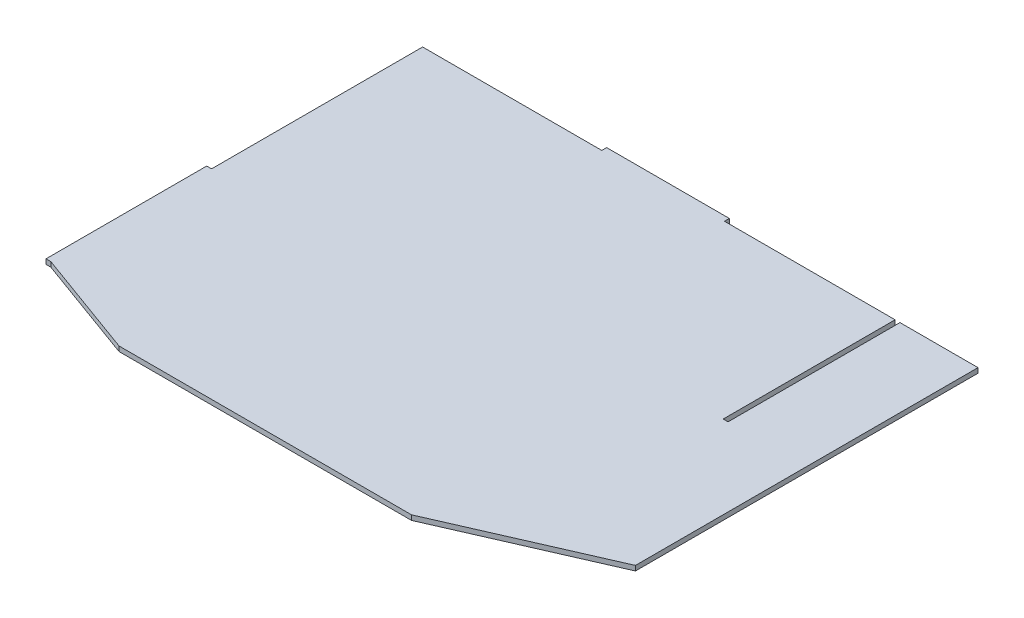
SolidWorks part; units mm, degrees
material "6061-T6 (SS)"
ref_plane "X-Y Datum" through (0, 0, 0) normal (0, 0, 1) x (1, 0, 0)
ref_plane "X-Z Datum" through (0, 0, 0) normal (0, 1, 0) x (1, 0, 0)
ref_plane "Y-Z Datum" through (0, 0, 0) normal (1, 0, 0) x (0, 0, -1)
sketch "Sketch1" plane through (0, 0, 0) normal (0, 0, 1) x (1, 0, 0)
  line L1 (-154.0556, -1.5875) -> (154.0556, -1.5875)
  line L2 (-154.0556, -1.5875) -> (-154.0556, 1.5875)
  line L3 (-154.0556, 1.5875) -> (154.0556, 1.5875)
  line L4 (154.0556, -1.5875) -> (154.0556, 1.5875)
  line L5 (-154.0556, -1.5875) -> (154.0556, 1.5875) construction
  line L6 (-154.0556, 1.5875) -> (154.0556, -1.5875) construction
  point P0 (0, 0)
  dimension "D1" = 3.175
  dimension "D2" = 308.1112
extrude "Boss-Extrude1" add sketch "Sketch1" along normal blind 267.83
sketch "Sketch3" plane through (154.0556, 0, 0) normal (1, 0, 0) x (0, 0, -1)
  line L0 (-267.83, 1.5875) -> (0, 1.5875) construction
  line L1 (-267.83, -1.5875) -> (-112.128, -1.5875)
  line L2 (-267.83, -1.5875) -> (-267.83, 1.5875)
  line L3 (-267.83, 1.5875) -> (-112.128, 1.5875)
  line L4 (-112.128, -1.5875) -> (-112.128, 1.5875)
  dimension "D1" = 155.702
extrude "Boss-Extrude3" add sketch "Sketch3" along normal blind 3.175
sketch "Sketch4" plane through (0, 0, 267.83) normal (0, 0, 1) x (1, 0, 0)
  line L1 (157.2306, -1.5875) -> (208.1043, -1.5875)
  line L2 (157.2306, -1.5875) -> (157.2306, 1.5875)
  line L3 (157.2306, 1.5875) -> (208.1043, 1.5875)
  line L4 (208.1043, -1.5875) -> (208.1043, 1.5875)
  dimension "D1" = 3.175
  dimension "D2" = 50.8737
extrude "Boss-Extrude4" add sketch "Sketch4" against normal blind 267.83
sketch "Sketch6" plane through (0, 1.5875, 0) normal (0, 1, 0) x (1, 0, 0)
  line L0 (106.5043, -267.83) -> (106.5043, -223.38)
  line L1 (208.1043, -267.83) -> (-154.0556, -267.83) construction
  line L2 (208.1043, -223.38) -> (106.5043, -223.38)
  line L3 (208.1043, 0) -> (208.1043, -267.83) construction
  line L4 (106.5043, -267.83) -> (208.1043, -223.38)
  line M9 (-154.0556, -267.83) -> (208.1043, -267.83)
  line M10 (208.1043, -267.83) -> (208.1043, 0)
  dimension "D1" = 44.45
  dimension "D2" = 101.6
extrude "Cut-Extrude1" cut sketch "Sketch6" against normal through all contours L4 M9 M10 region at (174.2376, 1.5875, 253.0133)
sketch "Sketch8" plane through (0, 0, 0) normal (0, 0, -1) x (-1, 0, 0)
  line L1 (37.216, 1.5875) -> (-42.784, 1.5875)
  line L2 (37.216, 1.5875) -> (37.216, -1.5875)
  line L3 (37.216, -1.5875) -> (-42.784, -1.5875)
  line L4 (-42.784, 1.5875) -> (-42.784, -1.5875)
extrude "Boss-Extrude6" add sketch "Sketch8" along normal blind 3.175
sketch "Sketch11" plane through (0, -1.5875, 0) normal (0, -1, 0) x (1, 0, 0)
  line L0 (-84.2056, 267.83) -> (-84.2056, 242.43)
  line L1 (-154.0556, 267.83) -> (106.5043, 267.83) construction
  line L2 (-154.0556, 242.43) -> (-84.2056, 242.43)
  line L3 (-154.0556, 267.83) -> (-154.0556, 0) construction
  line L4 (-154.0556, 242.43) -> (-84.2056, 267.83)
  line M4 (-154.0556, 267.83) -> (-154.0556, 0)
  line M18 (106.5043, 267.83) -> (-154.0556, 267.83)
  dimension "D1" = 69.85
  dimension "D2" = 25.4
extrude "Cut-Extrude3" cut sketch "Sketch11" against normal through all contours L4 M4 M18 region at (-130.7723, -1.5875, 259.3633)
sketch "Sketch13" plane through (-154.0556, 0, 0) normal (-1, 0, 0) x (0, 0, 1)
  line L1 (137.65, -1.598) -> (242.43, -1.598)
  line L2 (137.65, -1.598) -> (137.65, 1.5875)
  line L3 (137.65, 1.5875) -> (242.43, 1.5875)
  line L4 (242.43, -1.598) -> (242.43, 1.5875)
extrude "Boss-Extrude7" add sketch "Sketch13" along normal blind 3.175
